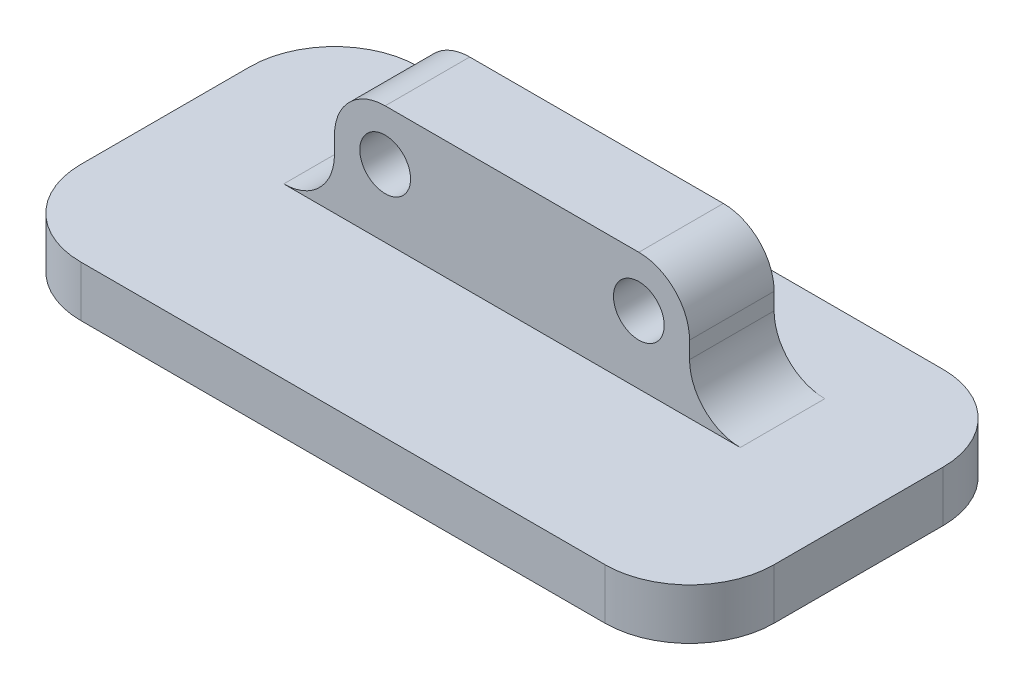
SolidWorks part; units mm, degrees
material "ABS"
ref_plane "正面" through (0, 0, 0) normal (0, 0, 1) x (1, 0, 0)
ref_plane "平面" through (0, 0, 0) normal (0, 1, 0) x (1, 0, 0)
ref_plane "右側面" through (0, 0, 0) normal (1, 0, 0) x (0, 0, -1)
sketch "ｽｹｯﾁ1" plane through (0, 0, 0) normal (0, 0, 1) x (1, 0, 0)
  line L1 (-3, -4) -> (18, -4)
  line L2 (-3, -4) -> (-3, 0)
  line L3 (0, 3) -> (15, 3)
  line L4 (18, -4) -> (18, 0)
  circle A0 centre (0, 0) radius 1.5
  circle A1 centre (15, 0) radius 1.5
  arc A2 (15, 3) -> (18, 0) centre (15, 0) cw
  arc A3 (-3, 0) -> (0, 3) centre (0, 0) cw
  dimension "D1" = 3
  dimension "D2" = 15
  dimension "D3" = 3
  dimension "D4" = 4
extrude "ﾎﾞｽ - 押し出し1" add sketch "ｽｹｯﾁ1" along normal blind 5
sketch "ｽｹｯﾁ2" plane through (0, -4, 0) normal (0, -1, 0) x (1, 0, 0)
  line L0 (-3, 5) -> (18, 5) construction
  line L1 (-13, -5) -> (28, -5)
  line L2 (-13, -5) -> (-13, 15)
  line L3 (-13, 15) -> (28, 15)
  line L4 (28, -5) -> (28, 15)
  line L5 (-3, 0) -> (18, 0) construction
  line L6 (-3, 5) -> (-3, 0) construction
  line L7 (18, 5) -> (18, 0) construction
  dimension "D1" = 5
  dimension "D2" = 10
  dimension "D3" = 10
  dimension "D4" = 10
extrude "ﾎﾞｽ - 押し出し2" add sketch "ｽｹｯﾁ2" along normal blind 3
fillet "ﾌｨﾚｯﾄ1" radius 3 2 edges at (-3, -4, 2.5) (18, -4, 2.5)
fillet "ﾌｨﾚｯﾄ2" radius 5 4 edges at (-13, -5.5, 15) (-13, -5.5, -5) (28, -5.5, 15) (28, -5.5, -5)
